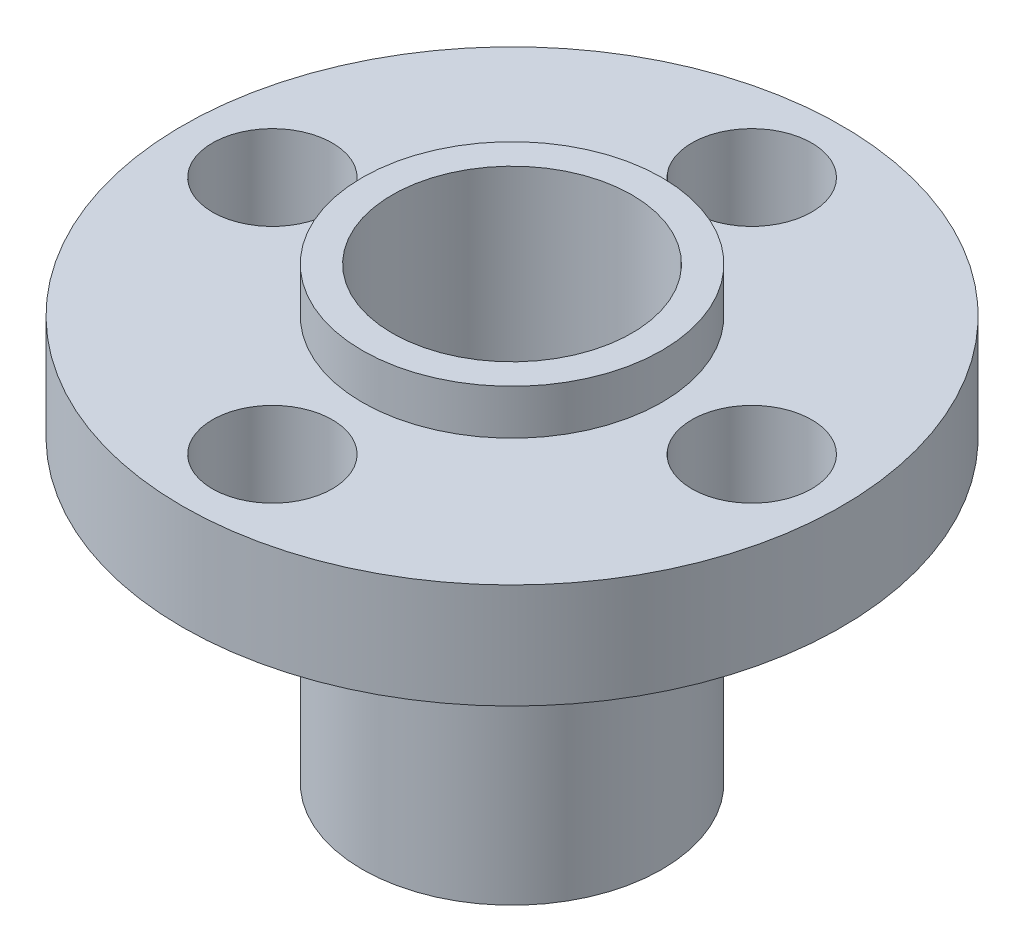
SolidWorks part; units mm, degrees
ref_plane "前视基准面" through (0, 0, 0) normal (0, 0, 1) x (1, 0, 0)
ref_plane "上视基准面" through (0, 0, 0) normal (0, 1, 0) x (1, 0, 0)
ref_plane "右视基准面" through (0, 0, 0) normal (1, 0, 0) x (0, 0, -1)
sketch "草图1" plane through (0, 0, 0) normal (0, 1, 0) x (1, 0, 0)
  circle A0 centre (0, 0) radius 5
  circle A1 centre (0, 0) radius 4
  circle A2 centre (0, 0) radius 8 construction
  circle A3 centre (0, 0) radius 11
  circle A4 centre (0, 8) radius 2
  circle A5 centre (8, 0) radius 2
  circle A6 centre (0, -8) radius 2
  circle A7 centre (-8, 0) radius 2
extrude "凸台-拉伸1" add sketch "草图1" along normal blind 3.5 contours A3 A7 A6 A5 A4 A0 region at (-10.6889, 0, 0)
extrude "凸台-拉伸2" add sketch "草图1<3>" along normal blind 5 contours A0 A1 region at (-4.8586, 0, 0)
sketch "草图1<3>" plane through (0, 0, 0) normal (0, 1, 0) x (1, 0, 0) same geometry as "草图1"
extrude "凸台-拉伸3" add sketch "草图1<4>" against normal blind 10 contours A0 A1 region at (-4.8586, 0, 0)
sketch "草图1<4>" plane through (0, 0, 0) normal (0, 1, 0) x (1, 0, 0) same geometry as "草图1"
